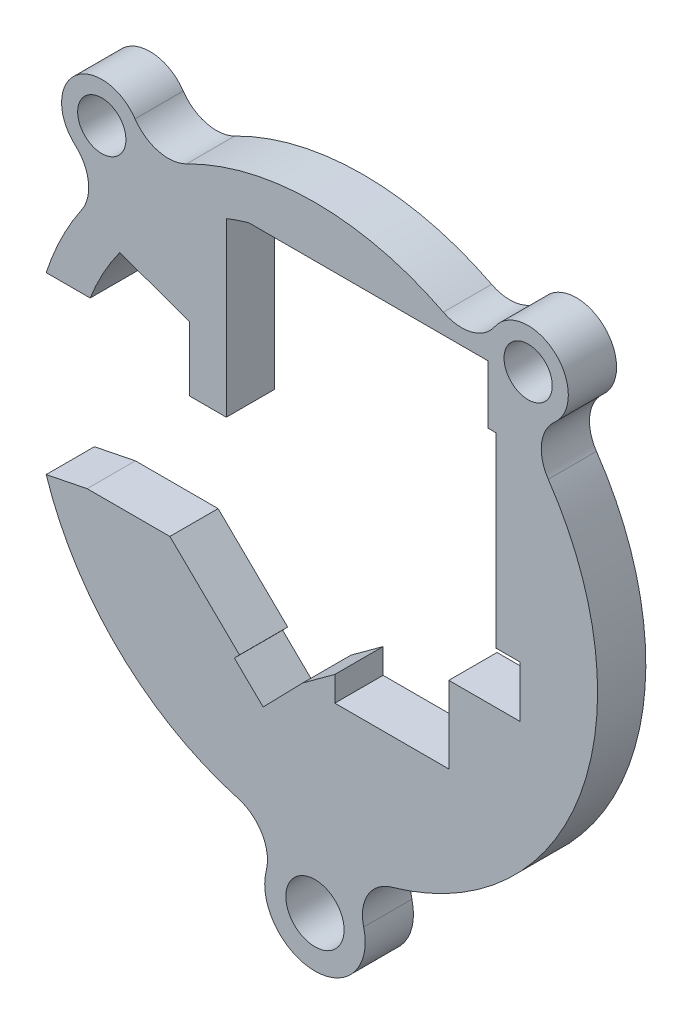
SolidWorks part; units mm, degrees
ref_plane "Front Plane" through (0, 0, 0) normal (0, 0, 1) x (1, 0, 0)
ref_plane "Top Plane" through (0, 0, 0) normal (0, 1, 0) x (1, 0, 0)
ref_plane "Right Plane" through (0, 0, 0) normal (1, 0, 0) x (0, 0, -1)
sketch "Sketch1" plane through (0, 0, 0) normal (0, 0, 1) x (1, 0, 0)
  line L1 (-14.9521, -2.9485) -> (-16.9841, -2.9485)
  line L2 (-16.9841, 2.9485) -> (-16.9841, 5.5245)
  line L3 (-14.9521, 2.9485) -> (-16.9841, 2.9485)
  line L4 (-16.9841, 5.5245) -> (-21.1739, 5.5245)
  line L5 (-16.9841, -2.9485) -> (-16.9841, -5.5245)
  line L6 (-16.9841, -5.5245) -> (-20.8712, -5.5245)
  line L7 (-15.24, 0) -> (-21.59, 0) construction
  line B0 (-15.24, 18.2372) -> (15.24, 18.2372)
  line B1 (11.43, 14.6558) -> (11.43, -0.8128)
  line B2 (0, 18.2372) -> (0, 0) construction
  line B3 (-5.6007, 14.1736) -> (-5.6007, -0.8128)
  line B4 (11.43, 14.6558) -> (-4.1791, 14.6558)
  line B5 (-5.6007, -0.8128) -> (11.43, -0.8128)
  line B6 (8.4582, -4.064) -> (12.9413, -4.064)
  line B7 (11.43, -0.8128) -> (12.9413, -0.8128)
  line B8 (12.9413, -0.8128) -> (12.9413, -4.064)
  line B9 (8.4582, -7.3406) -> (1.2573, -7.3406)
  line B10 (8.4582, -4.064) -> (8.4582, -7.3406)
  line B11 (-4.3942, -0.8128) -> (-4.3942, -4.064)
  line B12 (-4.3942, -4.064) -> (1.2573, -4.064)
  line B13 (1.2573, -4.064) -> (1.2573, -7.3406)
  line B14 (-0.7747, -8.8265) -> (-3.2737, -11.3919)
  line B15 (-0.7747, -8.8265) -> (-2.5941, -7.0541)
  line B16 (-2.5941, -7.0541) -> (-2.9176, -7.3862)
  line B17 (-2.9176, -7.3862) -> (-8.5123, -1.9362)
  line B18 (-8.5123, -1.9362) -> (-10.3645, -3.8375)
  line B19 (-10.3645, -3.8375) -> (-4.7697, -9.2875)
  line B20 (-4.7697, -9.2875) -> (-5.0932, -9.6195)
  line B21 (-5.0932, -9.6195) -> (-3.2737, -11.3919)
  line B22 (-12.3326, 18.2372) -> (-12.3326, 8.9535)
  line B23 (-7.9248, 18.2372) -> (-7.9248, 7.366) construction
  line B24 (-12.3326, 8.9535) -> (-7.9248, 7.366)
  line B25 (-5.6007, 3.302) -> (-7.9248, 3.302)
  line B26 (-7.9248, 3.302) -> (-7.9248, 7.366)
  line B27 (-14.3951, -5.0038) -> (-9.1672, -5.0038)
  line B28 (-0.7747, -8.8265) -> (1.2573, -7.3406)
  arc B29 (-3.302, 14.878) -> (3.302, 14.878) centre (0, 0) ccw
  circle B30 centre (0, -18.415) radius 1.4224
  circle B31 centre (0, 18.415) radius 1.4224
  circle B32 centre (0, 0) radius 21.59
  line B33 (1.2573, -8.9154) -> (8.4582, -8.9154)
  line B34 (1.2573, -7.3406) -> (1.2573, -8.9154)
  line B35 (8.4582, -7.3406) -> (8.4582, -8.9154)
  dimension "D1" = 2.032
  dimension "D2" = 11.049
sketch_block_instance "Block1-1"
sketch_block "Block1" parameters "D1"=3.81, "D2"=30.48, "D3"=3.5814, "D4"=9.6393, "D5"=19.05, "D6"=22.3012, "D7"=1.5113, "D8"=4.4831, "D9"=6.5278, "D10"=7.2009, "D11"=5.6515, "D12"=27.0637, "D13"=29.6291, "D14"=3.5814, "D15"=14.4653, "D16"=2.54, "D17"=2.6543, "D18"=10.3505, "D19"=9.2837, "D20"=10.8712, "D21"=7.3152, "D22"=14.9352, "D23"=23.241
extrude "Boss-Extrude1" add sketch "Sketch1" along normal blind 3.048 contours B0 B32 B29 B4 B1 B31 B30 | B27 B29 B1 B7 B8 B6 B10 B9 B28 B14 B21 B20 B19 | B3 B29 B24 B26 B25 | B0 B32 B31 | B22 B32 L4 L2 L3 B29 region at (-15.2714, -4.1381, 0) region at (-15.71, 9.7203, 0) region at (-11.7811, -5.3936, 0) region at (-7.7282, 8.9883, 0) region at (0, 21.3565, 0)
sketch "Sketch2" plane through (0, 0, 3.048) normal (0, 0, 1) x (1, 0, 0)
  line L0 (-14.3951, -5.0038) -> (-16.9841, -5.5245)
  line L2 (-16.9841, 5.5245) -> (-14.2034, 5.5245)
  line L3 (-14.3951, -5.0038) -> (-14.2034, 5.5245)
  line L4 (-16.9841, -5.5245) -> (-16.9841, 5.5245)
  arc A0 (-12.3326, 8.9535) -> (-14.9521, 2.9485) centre (0, 0) ccw construction
extrude "Cut-Extrude1" cut sketch "Sketch2" against normal through all
sketch "Sketch3" plane through (0, 0, 3.048) normal (0, 0, 1) x (1, 0, 0)
  line L0 (0, 0) -> (11.43, 14.6558) construction
  line L1 (0, 0) -> (-14.0833, 10.9835) construction
  line L2 (0, 0) -> (-10.9835, -14.0833) construction
  line L3 (0, 0) -> (14.0833, -10.9835) construction
  circle A0 centre (0, 0) radius 17.86
  circle A1 centre (0, 0) radius 21.59
extrude "Cut-Extrude2" cut sketch "Sketch3" against normal through all
sketch "Sketch4" plane through (0, 0, 3.048) normal (0, 0, 1) x (1, 0, 0)
  line L0 (0, -21.035) -> (0, 0) construction
  line L6 (10.2071, 14.6558) -> (11.43, 14.6558)
  line L7 (11.43, 14.6558) -> (11.43, 13.7235)
  line L19 (-21.6223, 17.86) -> (27.8478, 17.86) construction
  circle A0 centre (0, 0) radius 17.86
  circle A1 centre (13.4706, 15.32) radius 1.524
  circle A2 centre (-13.4706, 15.32) radius 2.54
  circle A3 centre (13.4706, 15.32) radius 2.54
  circle A4 centre (-16.8382, 11.5166) radius 2.54
  circle A5 centre (-9.2677, 18.1733) radius 2.54
  circle A6 centre (-13.4706, 15.32) radius 1.524
  circle A7 centre (0, -21.035) radius 1.8415
  circle A8 centre (0, -21.035) radius 3.175
  circle A9 centre (9.2677, 18.1733) radius 2.54
  circle A11 centre (16.8382, 11.5166) radius 2.54
  arc A12 (-1.2889, 17.8134) -> (1.2889, 17.8134) centre (0, 18.415) ccw
  arc A13 (-1.2889, 17.8134) -> (1.2889, 17.8134) centre (0, 18.415) ccw construction
  circle A14 centre (5.5404, -19.6332) radius 2.54
  circle A15 centre (-5.5404, -19.6332) radius 2.54
  arc M3 (-1.2889, -17.8134) -> (1.2889, -17.8134) centre (0, -18.415) cw
  arc M4 (1.2889, -17.8134) -> (11.43, 13.7235) centre (0, 0) ccw
  dimension "D2" = 3.048
  dimension "D4" = 5.08
  dimension "D3" = 3.683
  dimension "D1" = 5.08
  dimension "D5" = 6.35
  dimension "D6" = 5.08
extrude "Boss-Extrude3" add sketch "Sketch4" against normal blind 3.048 contours A5 A2 A0 | A2 A6 | A4 A0 A2 | A0 A12 | A9 A0 L6 A3 | L7 A3 L6 A1 | A11 A3 L7 A0 | A8 A7 | A15 A8 A0 | A14 A0 A8 M4 | A0 M3 | A3 L7 A0 region at (10.2151, 15.3737, 3.048) region at (11.0363, 15.7276, 3.048) region at (11.5182, 13.6739, 3.048) region at (13.7616, 12.185, 3.048) region at (0, 17.4932, 3.048) region at (-10.3242, 15.2074, 3.048) region at (2.6103, -18.2487, 3.048) region at (-13.7616, 12.185, 3.048) region at (-13.4749, 12.8518, 3.048) region at (0, -17.4932, 3.048) region at (3.0615, -20.6537, 3.048) region at (-2.6103, -18.2487, 3.048)
sketch "Sketch7" plane through (0, 0, 3.048) normal (0, 0, 1) x (1, 0, 0)
  line L1 (11.43, 14.6558) -> (10.922, 14.6558)
  line L2 (11.43, 14.6558) -> (11.43, 10.9728)
  line L3 (11.43, 10.9728) -> (10.922, 10.9728)
  line L4 (10.922, 14.6558) -> (10.922, 10.9728)
  dimension "D1" = 0.508
  dimension "D2" = 3.683
extrude "Boss-Extrude4" add sketch "Sketch7" against normal up to vertex (3.048 mm away) up to point (11.43, 14.6558, 0)
sketch "Sketch8" plane through (0, 0, 3.048) normal (0, 0, 1) x (1, 0, 0)
  line L0 (-15.24, 18.2372) -> (15.24, 18.2372) construction
  line L1 (-15.24, 18.2372) -> (15.24, 18.2372)
  line L2 (0, 18.2372) -> (0, -12.1158) construction
  line L3 (10.8325, 18.2372) -> (10.8325, -6.5024) construction
  line L4 (0, 0) -> (14.5917, -10.2986) construction
  line L5 (-8.579, 11.2522) -> (-8.579, 18.2372) construction
  circle A0 centre (0, -13.2588) radius 1.143
  circle A1 centre (10.8325, -7.6454) radius 1.143
  arc A2 (4.8506, -17.1887) -> (14.7417, 10.0827) centre (0, 0) ccw construction
  circle A3 centre (-8.579, 10.1092) radius 1.143
  circle A4 centre (0, 0) radius 15.2591 construction
  circle A5 centre (0, 0) radius 13.2588 construction
  dimension "D2" = 2.286
  dimension "D4" = 6.985
  dimension "D5" = 30.5181
  dimension "D1" = 30.353
  dimension "D3" = 24.7396
extrude "Cut-Extrude3" [suppressed] cut sketch "Sketch8" against normal through all contours A0 | A1 | A3
sketch "Sketch9" plane through (0, 0, 3.048) normal (0, 0, 1) x (1, 0, 0)
  line B0 (-12.3326, 8.9535) -> (-7.9248, 7.366)
  line B1 (-7.9248, 3.302) -> (-7.9248, 7.366)
  line B2 (-14.2034, 5.5245) -> (-16.9841, 5.5245)
  line B3 (-16.9841, -5.5245) -> (-14.3951, -5.0038)
  line B4 (-14.3951, -5.0038) -> (-9.1672, -5.0038)
  line B5 (-9.1672, -5.0038) -> (-4.7697, -9.2875)
  line B6 (-4.7697, -9.2875) -> (-5.0932, -9.6195)
  line B7 (-5.0932, -9.6195) -> (-3.2737, -11.3919)
  line B8 (-0.7747, -8.8265) -> (-3.2737, -11.3919)
  line B9 (-0.7747, -8.8265) -> (1.2573, -7.3406)
  line B10 (1.2573, -7.3406) -> (1.2573, -8.9154)
  line B11 (1.2573, -8.9154) -> (8.4582, -8.9154)
  line B12 (8.4582, -4.064) -> (8.4582, -8.9154)
  line B13 (8.4582, -4.064) -> (12.9413, -4.064)
  line B14 (12.9413, -0.8128) -> (12.9413, -4.064)
  line B15 (11.43, -0.8128) -> (12.9413, -0.8128)
  line B16 (11.43, 10.9728) -> (11.43, -0.8128)
  line B17 (10.922, 10.9728) -> (11.43, 10.9728)
  line B18 (10.922, 14.6558) -> (10.922, 10.9728)
  line B19 (-4.1791, 14.6558) -> (10.922, 14.6558)
  line B20 (-5.6007, 14.1736) -> (-5.6007, 3.302)
  line B21 (-5.6007, 3.302) -> (-7.9248, 3.302)
  circle B22 centre (-8.579, 10.1092) radius 1.143
  arc B23 (-12.3326, 8.9535) -> (-14.2034, 5.5245) centre (0, 0) ccw
  arc B24 (-4.1791, 14.6558) -> (-5.6007, 14.1736) centre (0, 0) ccw
  circle B25 centre (10.8325, -7.6454) radius 1.143
  circle B26 centre (0, -13.2588) radius 1.143
sketch_block_instance "Block2-1"
sketch_block "Block2"
